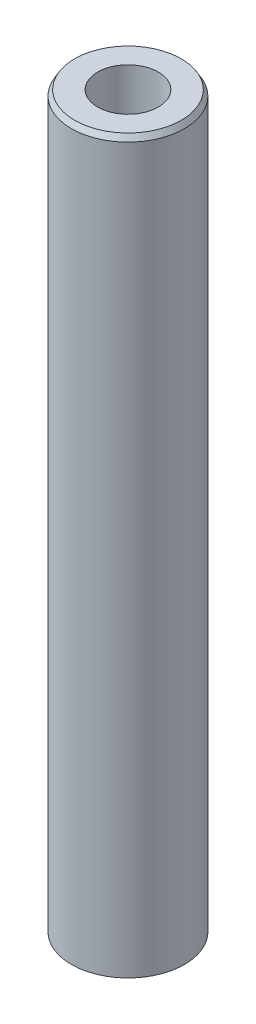
SolidWorks part; units mm, degrees
ref_plane "Front Plane" through (0, 0, 0) normal (0, 0, 1) x (1, 0, 0)
ref_plane "Top Plane" through (0, 0, 0) normal (0, 1, 0) x (1, 0, 0)
ref_plane "Right Plane" through (0, 0, 0) normal (1, 0, 0) x (0, 0, -1)
sketch "Sketch1" plane through (0, 0, 0) normal (0, 1, 0) x (1, 0, 0)
  circle A0 centre (0, 0) radius 27.5
  dimension "SHAFT_OD" = 55
extrude "Boss-Extrude1" add sketch "Sketch1" along normal blind 356.323
sketch "Sketch2" plane through (0, 0, 0) normal (0, 1, 0) x (1, 0, 0)
  circle A0 centre (0, 0) radius 14.7516
  dimension "BORE_D" = 29.5033
extrude "Cut-Extrude1" cut sketch "Sketch2" along normal through all
chamfer "Chamfer1" distance 2.7296 angle 30 2 edges at (0, 356.323, 27.5) (0, 0, 27.5) first distance on face at (0, 356.323, 27.5) first distance on face at (0, 0, 14.7516)
